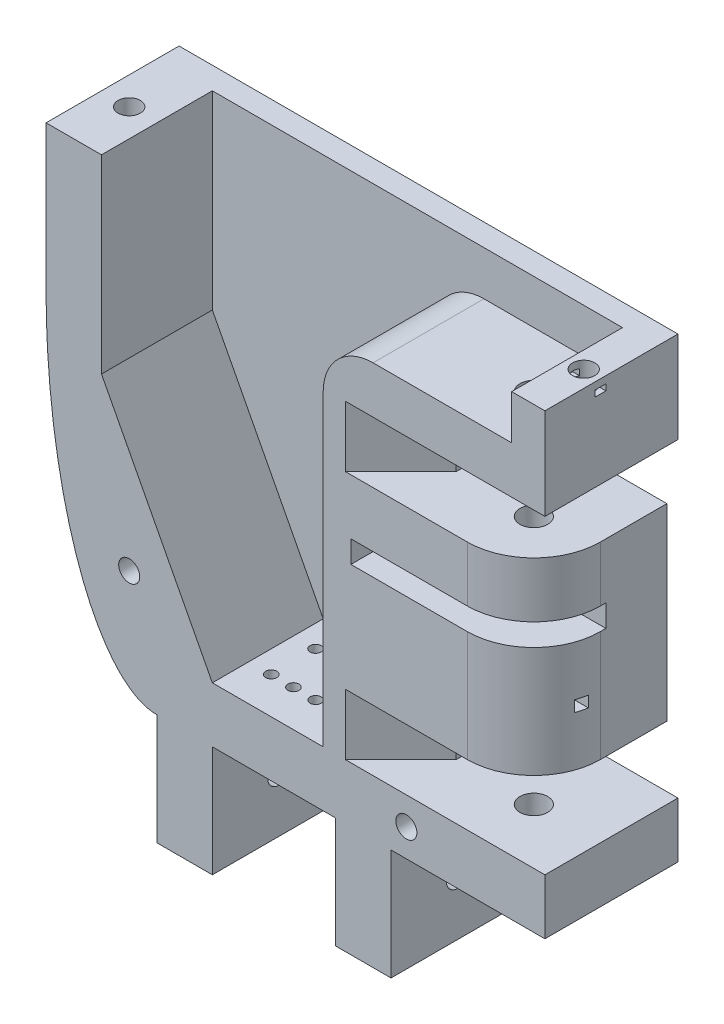
SolidWorks part; units mm, degrees
ref_plane "Front Plane" through (0, 0, 0) normal (0, 0, 1) x (1, 0, 0)
ref_plane "Top Plane" through (0, 0, 0) normal (0, 1, 0) x (1, 0, 0)
ref_plane "Right Plane" through (0, 0, 0) normal (1, 0, 0) x (0, 0, -1)
sketch "Sketch2" plane through (0, 0, 0) normal (0, 0, 1) x (1, 0, 0)
  line L1 (0, 0) -> (114.3, 0)
  line L2 (0, 0) -> (0, 142.875)
  line L3 (0, 142.875) -> (114.3, 142.875)
  line L4 (114.3, 0) -> (114.3, 142.875)
  dimension "D1" = 114.3
  dimension "D2" = 142.875
extrude "Boss-Extrude2" add sketch "Sketch2" along normal blind 30.48 contours L3 L4 L1 L2
fillet "Fillet1" radius 71.501 1 edges at (0, 0, 15.24) second distance 25.4 first distance on face at (0, 71.4375, 15.24)
sketch "Sketch3" plane through (0, 142.875, 0) normal (0, 1, 0) x (1, 0, 0)
  line L0 (0, -30.48) -> (114.3, -30.48) construction
  line L1 (33.8666, -7.62) -> (33.8666, -27.94)
  line L10 (0, -30.48) -> (0, 0) construction
  line L13 (49.1066, -7.62) -> (49.1066, -27.94)
  arc A8 (33.8666, -7.62) -> (33.8666, -27.94) centre (41.4866, -17.78) ccw
  arc A9 (49.1066, -27.94) -> (49.1066, -7.62) centre (41.4866, -17.78) ccw
  dimension "D1" = 25.4
  dimension "D2" = 12.7
  dimension "D3" = 41.4866
  dimension "D5" = 7.62
  dimension "D6" = 7.62
extrude "Boss-Extrude3" add sketch "Sketch3" along normal blind 11.43
sketch "Sketch5" plane through (0, 0, 30.48) normal (0, 0, 1) x (1, 0, 0)
  line L0 (62.6533, 142.875) -> (77.8933, 142.875)
  line L1 (0, 142.875) -> (114.3, 142.875) construction
  line L2 (0, 71.501) -> (0, 142.875) construction
  line L3 (114.3, 0) -> (114.3, 142.875) construction
  line L4 (91.44, 143.0325) -> (106.68, 143.0325)
  arc A0 (62.6533, 142.875) -> (77.8933, 142.875) centre (70.2733, 132.3992) ccw
  arc A1 (91.44, 143.0325) -> (106.68, 143.0325) centre (99.06, 132.5567) ccw
  dimension "D1" = 25.908
  dimension "D5" = 25.908
  dimension "D2" = 15.24
  dimension "D3" = 0
  dimension "D4" = 70.2733
  dimension "D6" = 15.24
  dimension "D7" = 15.24
extrude "Cut-Extrude2" cut sketch "Sketch5" against normal blind 25.4
fillet "Fillet2" radius 1.27 3 edges at (91.2281, 142.875, 17.78) (77.8933, 142.875, 17.78) (62.6533, 142.875, 17.78)
sketch "Sketch7" plane through (0, 142.875, 0) normal (0, 1, 0) x (1, 0, 0)
  line L0 (0, -30.48) -> (59.4301, -30.48) construction
  line L1 (0, 0) -> (27.94, 0)
  line L2 (0, 0) -> (0, -30.48)
  line L3 (0, -30.48) -> (27.94, -30.48)
  line L4 (27.94, 0) -> (27.94, -30.48)
  dimension "D1" = 27.94
extrude "Cut-Extrude4" cut sketch "Sketch7" against normal blind 12.7
sketch "Sketch8" plane through (0, 130.175, 0) normal (0, 1, 0) x (1, 0, 0)
  line L6 (0, -30.48) -> (27.94, -30.48) construction
  line L7 (0, 0) -> (0, -30.48) construction
  line L8 (5.08, -7.62) -> (5.08, -27.94)
  line L9 (20.32, -7.62) -> (20.32, -27.94)
  arc A4 (5.08, -7.62) -> (5.08, -27.94) centre (12.7, -17.78) ccw
  arc A5 (20.32, -27.94) -> (20.32, -7.62) centre (12.7, -17.78) ccw
  dimension "D1" = 25.4
  dimension "D2" = 12.7
  dimension "D3" = 12.7
  dimension "D4" = 7.62
  dimension "D5" = 7.62
extrude "Boss-Extrude4" add sketch "Sketch8" along normal blind 11.43
sketch "Sketch10" plane through (0, 0, 30.48) normal (0, 0, 1) x (1, 0, 0)
  line L0 (114.3, 0) -> (114.3, 142.875) construction
  line L1 (63.5, 109.855) -> (12.7, 109.855)
  line L3 (63.5, 12.7) -> (38.1, 12.7)
  line L4 (12.7, 109.855) -> (12.7, 61.2775)
  line L5 (0, 71.501) -> (0, 130.175) construction
  line L6 (25.4, 0) -> (114.3, 0) construction
  line L7 (27.94, 142.875) -> (59.4301, 142.875) construction
  line L8 (12.7, 61.2775) -> (38.1, 12.7)
  line L14 (63.5, 94.615) -> (63.5, 12.7)
  line L15 (63.5, 109.855) -> (106.68, 109.855)
  line L17 (63.5, 94.615) -> (106.68, 94.615)
  line L18 (106.68, 109.855) -> (106.68, 94.615)
  dimension "D1" = 7.62
  dimension "D2" = 12.7
  dimension "D3" = 12.7
  dimension "D4" = 33.02
  dimension "D5" = 15.24
extrude "Cut-Extrude6" cut sketch "Sketch10" against normal blind 25.4
sketch "Sketch11" plane through (49.1066, 0, 0) normal (-1, 0, 0) x (0, 0, 1)
  line L0 (7.62, 154.305) -> (27.94, 154.305) construction
  line L1 (27.94, 154.305) -> (27.94, 142.875) construction
  line L2 (27.94, 154.305) -> (7.62, 154.305) construction
  line L3 (22.0449, 151.9849) -> (27.94, 142.875)
  line L4 (27.94, 142.875) -> (27.94, 154.305)
  line L5 (27.94, 154.305) -> (17.78, 154.305)
  circle A0 centre (17.78, 149.225) radius 3.175
  arc A1 (17.78, 154.305) -> (22.0449, 151.9849) centre (17.78, 149.225) cw
  dimension "D2" = 6.35
  dimension "D1" = 5.08
  dimension "D3" = 10.16
extrude "Cut-Extrude7" cut sketch "Sketch11" against normal through all both and the other way through all
sketch "Sketch12" plane through (20.32, 0, 0) normal (-1, 0, 0) x (0, 0, 1)
  line L0 (27.94, 141.605) -> (27.94, 130.175) construction
  line L1 (7.62, 141.605) -> (27.94, 141.605) construction
  line L2 (27.94, 141.605) -> (7.62, 141.605) construction
  line L3 (22.0449, 139.2849) -> (27.94, 130.175)
  line L4 (27.94, 130.175) -> (27.94, 141.605)
  line L5 (27.94, 141.605) -> (17.78, 141.605)
  circle A0 centre (17.78, 136.525) radius 3.175
  arc A1 (17.78, 141.605) -> (22.0449, 139.2849) centre (17.78, 136.525) cw
  dimension "D1" = 6.35
  dimension "D2" = 10.16
  dimension "D3" = 5.08
extrude "Cut-Extrude8" cut sketch "Sketch12" against normal up to surface (7.62 mm away) and the other way through all up to face at (27.94, 136.525, 15.24)
chamfer "Chamfer1" distance 12.7 distance2 2.54 1 edges at (27.94, 130.175, 15.24) first distance on face at (27.94, 136.525, 15.24)
sketch "Sketch13" plane through (0, 0, 30.48) normal (0, 0, 1) x (1, 0, 0)
  line L1 (114.3, 142.875) -> (106.68, 142.875)
  line L2 (114.3, 142.875) -> (114.3, 137.795)
  line L3 (114.3, 137.795) -> (106.68, 137.795)
  line L4 (106.68, 142.875) -> (106.68, 137.795)
  dimension "D1" = 7.62
  dimension "D2" = 5.08
extrude "Cut-Extrude9" cut sketch "Sketch13" against normal up to surface (25.4 mm away) up to face at (95.7606, 134.9038, 5.08)
fillet "Fillet4" radius 1.27 2 edges at (114.3, 137.795, 17.78) (110.9076, 137.795, 17.78)
sketch "Sketch14" plane through (0, 0, 30.48) normal (0, 0, 1) x (1, 0, 0)
  line L0 (114.3, 0) -> (114.3, 136.525) construction
  line L1 (114.3, 12.7) -> (81.28, 12.7)
  line L2 (114.3, 12.7) -> (114.3, 83.82)
  line L3 (114.3, 83.82) -> (81.28, 83.82)
  line L4 (81.28, 12.7) -> (81.28, 26.67)
  line L5 (25.4, 0) -> (114.3, 0) construction
  line L6 (81.28, 69.85) -> (81.28, 83.82)
  line L7 (81.28, 69.85) -> (111.76, 69.85)
  line L9 (81.28, 26.67) -> (111.76, 26.67)
  line L10 (111.76, 69.85) -> (111.76, 26.67)
  dimension "D1" = 12.7
  dimension "D2" = 71.12
  dimension "D3" = 33.02
  dimension "D4" = 13.97
  dimension "D5" = 13.97
  dimension "D6" = 30.48
extrude "Cut-Extrude10" cut sketch "Sketch14" against normal through all
chamfer "Chamfer2" distance 12.7 distance2 12.7 2 edges at (81.28, 19.685, 30.48) (81.28, 76.835, 30.48)
sketch "Sketch15" plane through (0, 0, 0) normal (0, -1, 0) x (1, 0, 0)
  line L0 (114.3, 30.48) -> (114.3, 0) construction
  line L1 (25.4, 30.48) -> (114.3, 30.48) construction
  circle A0 centre (99.06, 17.78) radius 3.175
  dimension "D1" = 6.35
  dimension "D2" = 15.24
  dimension "D3" = 12.7
extrude "Cut-Extrude11" cut sketch "Sketch15" against normal up to surface (109.855 mm away) up to face at (59.69, 109.855, 17.78)
sketch "Sketch16" plane through (0, 141.605, 0) normal (0, 1, 0) x (1, 0, 0)
  line L0 (0.407, -14.5906) -> (5.08, -14.605)
  line L1 (5.08, -14.605) -> (5.08, -7.62)
  line L2 (20.32, -14.605) -> (24.9967, -14.605)
  line L3 (20.32, -7.62) -> (20.32, -17.78) construction
  line L4 (20.32, -7.62) -> (20.32, -14.605)
  arc A0 (24.9967, -14.605) -> (20.32, -7.62) centre (12.7, -17.78) ccw
  arc A1 (5.08, -7.62) -> (0.407, -14.5906) centre (12.7, -17.78) ccw
extrude "Boss-Extrude5" add sketch "Sketch16" along normal blind 1.27
chamfer "Chamfer3" distance 1.27 angle 45 2 edges at (22.6584, 142.875, 14.605) (2.7435, 142.875, 14.5978)
sketch "Sketch17" plane through (0, 154.305, 0) normal (0, 1, 0) x (1, 0, 0)
  line L0 (29.1505, -14.7614) -> (33.8666, -14.7614)
  line L1 (33.8666, -17.78) -> (33.8666, -7.62) construction
  line L2 (33.8666, -14.7614) -> (33.8666, -7.62)
  line L4 (49.1066, -14.7614) -> (53.8226, -14.7614)
  line L5 (49.1066, -7.62) -> (49.1066, -17.78) construction
  line L6 (49.1066, -7.62) -> (49.1066, -14.7614)
  arc A0 (33.8666, -7.62) -> (29.1505, -14.7614) centre (41.4866, -17.78) ccw
  arc A1 (53.8226, -14.7614) -> (49.1066, -7.62) centre (41.4866, -17.78) ccw
extrude "Boss-Extrude6" add sketch "Sketch17" along normal blind 1.27
chamfer "Chamfer4" distance 1.27 angle 45 2 edges at (51.4646, 155.575, 14.7614) (31.5086, 155.575, 14.7614)
fillet "Fillet5" radius 15.24 1 edges at (111.76, 48.26, 30.48)
sketch "Sketch19" plane through (0, 0, 30.48) normal (0, 0, 1) x (1, 0, 0)
  line L0 (111.76, 69.85) -> (111.76, 26.67) construction
  line L1 (81.28, 52.07) -> (111.76, 52.07)
  line L3 (81.28, 57.15) -> (111.76, 57.15)
  line L4 (111.76, 52.07) -> (111.76, 57.15)
  line L5 (81.28, 52.07) -> (111.76, 57.15) construction
  line L6 (81.28, 57.15) -> (111.76, 52.07) construction
  line L7 (68.58, 69.85) -> (96.52, 69.85) construction
  line L9 (81.28, 57.15) -> (69.85, 57.15)
  line L11 (81.28, 52.07) -> (69.85, 52.07)
  line L12 (69.85, 57.15) -> (69.85, 52.07)
  point P0 (96.52, 54.61)
  dimension "D1" = 15.24
  dimension "D2" = 5.08
  dimension "D3" = 12.7
  dimension "D4" = 11.43
extrude "Cut-Extrude12" cut sketch "Sketch19" against normal blind 16.51
sketch "Sketch20" plane through (63.5, 0, 0) normal (-1, 0, 0) x (0, 0, 1)
  line L0 (30.48, 12.7) -> (30.48, 94.615) construction
  line L1 (17.78, 40.64) -> (20.32, 40.64)
  line L2 (17.78, 40.64) -> (17.78, 38.1)
  line L3 (17.78, 38.1) -> (20.32, 38.1)
  line L4 (20.32, 40.64) -> (20.32, 38.1)
  line L5 (5.08, 12.7) -> (30.48, 12.7) construction
  dimension "D1" = 2.54
  dimension "D2" = 2.54
  dimension "D3" = 12.7
  dimension "D4" = 25.4
extrude "Cut-Extrude13" cut sketch "Sketch20" against normal through all
fillet "Fillet6" radius 1.27 1 edges at (63.5, 38.1, 19.05)
ref_plane "Plane1" through (0, 0, 17.78) normal (0, 0, 1) x (1, 0, 0)
sketch "Sketch21" plane through (0, 0, 17.78) normal (0, 0, 1) x (1, 0, 0)
  line L0 (12.7, 109.855) -> (10.4859, 130.175)
  line L1 (0, 130.175) -> (25.4, 130.175) construction
  line L2 (10.4859, 130.175) -> (15.5659, 130.175)
  line L3 (15.5659, 130.175) -> (17.78, 109.855)
  line L4 (106.68, 109.855) -> (12.7, 109.855) construction
  line L5 (17.78, 109.855) -> (12.7, 109.855)
  line L6 (55.4297, 142.875) -> (50.8604, 121.6537)
  line L7 (27.94, 142.875) -> (59.4301, 142.875) construction
  line L8 (38.9466, 142.875) -> (44.0266, 142.875)
  line L9 (38.9466, 142.875) -> (38.9466, 109.855)
  line L10 (38.9466, 109.855) -> (44.0266, 109.855)
  line L11 (44.0266, 142.875) -> (44.0266, 109.855)
  line L12 (33.8666, 151.9849) -> (33.8666, 142.875) construction
  line L13 (50.8604, 121.6537) -> (50.8604, 109.855)
  line L14 (66.8866, 119.8958) -> (71.9666, 119.8958)
  line L15 (66.8866, 119.8958) -> (66.8866, 109.855)
  line L16 (66.8866, 109.855) -> (71.9666, 109.855)
  line L17 (71.9666, 119.8958) -> (71.9666, 109.855)
  line L18 (96.0966, 119.9462) -> (101.1766, 119.9462)
  line L19 (96.0966, 119.9462) -> (96.0966, 109.855)
  line L20 (96.0966, 109.855) -> (101.1766, 109.855)
  line L21 (101.1766, 119.9462) -> (101.1766, 109.855)
  line L22 (50.8604, 109.855) -> (52.4497, 109.855)
  line L23 (52.4497, 109.855) -> (52.4497, 121.6537)
  line L24 (52.4497, 121.6537) -> (57.0191, 142.875)
  line L25 (57.0191, 142.875) -> (55.4297, 142.875)
  line L36 (106.68, 94.615) -> (106.68, 109.855) construction
  line L37 (106.68, 103.1464) -> (114.3, 103.1464)
  line L38 (106.68, 103.1464) -> (106.68, 101.7444)
  line L39 (106.68, 101.7444) -> (114.3, 101.7444)
  line L40 (114.3, 103.1464) -> (114.3, 101.7444)
  line L41 (114.3, 83.82) -> (114.3, 136.525) construction
  line L42 (81.1166, 142.875) -> (88.085, 142.875) construction
  line L43 (83.8937, 142.875) -> (85.379, 142.875)
  line L44 (83.8937, 142.875) -> (83.8937, 109.855)
  line L45 (83.8937, 109.855) -> (85.379, 109.855)
  line L46 (85.379, 142.875) -> (85.379, 109.855)
  arc A0 (60.3982, 140.7831) -> (80.1484, 140.7831) centre (70.2733, 132.3992) ccw construction
  arc A1 (89.0649, 140.7971) -> (111.4997, 136.1707) centre (99.06, 132.5567) ccw construction
  point P9 (13.0259, 130.175)
  dimension "D1" = 5.08
  dimension "D2" = 2.5251
  dimension "D3" = 5.08
  dimension "D4" = 5.08
  dimension "D5" = 5.08
  dimension "D6" = 22.86
  dimension "D7" = 5.08
  dimension "D8" = 24.13
extrude "Cut-Extrude14" cut sketch "Sketch21" against normal blind 1.27 and the other way blind 1.27
fillet "Fillet7" radius 11.43 1 edges at (63.5, 94.615, 17.78)
sketch "Sketch22" plane through (0, 12.7, 0) normal (0, 1, 0) x (1, 0, 0)
  line L0 (38.1, -5.08) -> (38.1, -30.48) construction
  circle A0 centre (43.18, -11.9083) radius 1.27
  circle A1 centre (48.26, -11.9083) radius 1.27
  circle A2 centre (53.34, -11.9083) radius 1.27
  circle A3 centre (58.42, -11.9083) radius 1.27
  circle A4 centre (43.18, -22.0683) radius 1.27
  circle A5 centre (48.26, -22.0683) radius 1.27
  circle A6 centre (53.34, -22.0683) radius 1.27
  circle A7 centre (58.42, -22.0683) radius 1.27
  dimension "D1" = 2.54
  dimension "D2" = 2.54
  dimension "D3" = 2.54
  dimension "D4" = 2.54
  dimension "D5" = 2.54
  dimension "D6" = 2.54
  dimension "D7" = 2.54
  dimension "D8" = 2.54
  dimension "D9" = 10.16
  dimension "D10" = 10.16
  dimension "D11" = 10.16
  dimension "D12" = 10.16
  dimension "D13" = 5.08
  dimension "D14" = 5.08
  dimension "D15" = 5.08
  dimension "D16" = 5.08
extrude "Cut-Extrude15" cut sketch "Sketch22" against normal up to surface (12.7 mm away) up to face at (99.06, 0, 14.605)
sketch "Sketch23" plane through (0, 0, 0) normal (0, 0, -1) x (-1, 0, 0)
  line L0 (0, 71.501) -> (0, 130.175) construction
  line L1 (-25.4, 0) -> (-114.3, 0) construction
  circle A0 centre (-25.4, 120.65) radius 2.413
  circle A1 centre (-19.05, 25.4) radius 2.413
  circle A2 centre (-82.55, 6.35) radius 2.413
  dimension "D1" = 4.826
  dimension "D4" = 4.826
  dimension "D9" = 4.826
  dimension "D2" = 25.4
  dimension "D3" = 120.65
  dimension "D5" = 19.05
  dimension "D6" = 25.4
  dimension "D7" = 6.35
  dimension "D8" = 82.55
extrude "Cut-Extrude16" cut sketch "Sketch23" against normal through all both and the other way through all
sketch "Sketch24" plane through (0, 0, 0) normal (0, -1, 0) x (1, 0, 0)
  line L0 (25.4, 0) -> (114.3, 0) construction
  line L1 (25.4, 30.48) -> (38.1, 30.48)
  line L2 (25.4, 30.48) -> (25.4, 0)
  line L3 (25.4, 0) -> (38.1, 0)
  line L4 (38.1, 30.48) -> (38.1, 0)
  line L5 (25.4, 30.48) -> (114.3, 30.48) construction
  line L6 (66.3452, 30.48) -> (79.0452, 30.48)
  line L7 (66.3452, 30.48) -> (66.3452, 0)
  line L8 (66.3452, 0) -> (79.0452, 0)
  line L9 (79.0452, 30.48) -> (79.0452, 0)
  dimension "D1" = 12.7
  dimension "D2" = 12.7
extrude "Boss-Extrude7" add sketch "Sketch24" along normal blind 25.4
sketch "Sketch25" plane through (79.0452, 0, 0) normal (1, 0, 0) x (0, 0, -1)
  line L0 (-30.48, -25.4) -> (0, -25.4) construction
  line L1 (0, -25.4) -> (0, 0) construction
  circle A0 centre (-15.24, -12.7) radius 2.54
  dimension "D3" = 5.08
  dimension "D1" = 12.7
  dimension "D2" = 15.24
extrude "Cut-Extrude17" cut sketch "Sketch25" against normal through all
sketch "Sketch26" plane through (0, 130.175, 0) normal (0, 1, 0) x (1, 0, 0)
  line L1 (-10.7727, 18.3031) -> (123.8383, 18.3031)
  line L2 (-10.7727, 18.3031) -> (-10.7727, -42.206)
  line L3 (-10.7727, -42.206) -> (123.8383, -42.206)
  line L4 (123.8383, 18.3031) -> (123.8383, -42.206)
extrude "Cut-Extrude18" cut sketch "Sketch26" against normal blind 25.4 and the other way blind 30.48
sketch "Sketch27" plane through (0, 104.775, 0) normal (0, 1, 0) x (1, 0, 0)
  line L0 (0, 0) -> (114.3, 0) construction
  line L2 (114.3, -30.48) -> (114.3, 0) construction
  line L3 (0, -30.48) -> (0, 0) construction
  circle A0 centre (6.35, -17.78) radius 2.54
  circle A1 centre (110.49, -17.78) radius 2.54
  point P4 (110.585, -17.8279)
  point P5 (110.9434, -17.6455)
  point P10 (0, 0)
  point P12 (0, 0)
  dimension "D1" = 17.78
  dimension "D2" = 17.78
  dimension "D3" = 3.81
  dimension "D4" = 6.35
extrude "Cut-Extrude19" cut sketch "Sketch27" against normal blind 5.08
